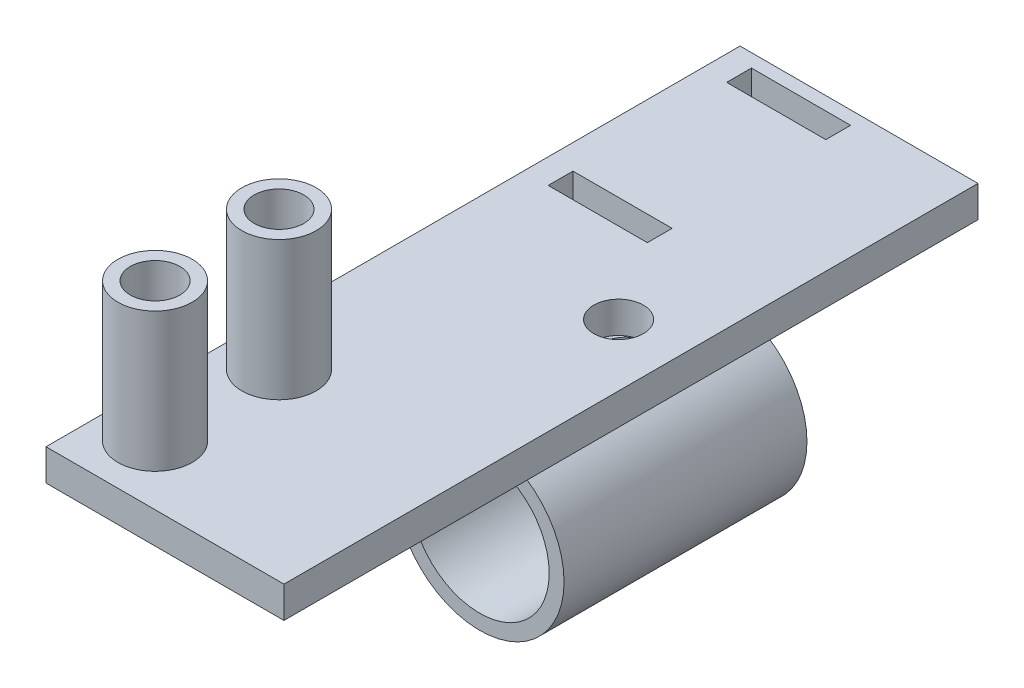
SolidWorks part; units mm, degrees
other "DetailItem2"
other "DetailItem3"
other "Weld Folder"
other "Weld Bead2"
other "Weld Bead3"
ref_plane "Front Plane" through (0, 0, 0) normal (0, 0, 1) x (1, 0, 0)
ref_plane "Top Plane" through (0, 0, 0) normal (0, 1, 0) x (1, 0, 0)
ref_plane "Right Plane" through (0, 0, 0) normal (1, 0, 0) x (0, 0, -1)
sketch "Sketch1" plane through (0, 0, 0) normal (0, 1, 0) x (1, 0, 0)
  line L0 (-59.4061, 36.8) -> (49940.5939, 36.8) construction
  line L1 (12.5, -80) -> (-35.5, -80)
  line L2 (12.5, -80) -> (12.5, 60)
  line L3 (12.5, 60) -> (-35.5, 60)
  line L4 (-35.5, -80) -> (-35.5, 60)
  line L5 (12.5, -80) -> (-35.5, 60) construction
  line L6 (12.5, 60) -> (-35.5, -80) construction
  line L7 (-30.5, 57.3) -> (-10.5, 57.3)
  line L8 (-30.5, 57.3) -> (-30.5, 52.3)
  line L9 (-30.5, 52.3) -> (-10.5, 52.3)
  line L10 (-10.5, 57.3) -> (-10.5, 52.3)
  line L11 (-30.5, 57.3) -> (-10.5, 52.3) construction
  line L12 (-30.5, 52.3) -> (-10.5, 57.3) construction
  line L13 (-10.5, 16.3) -> (-10.5, 21.3)
  line L14 (-30.5, 16.3) -> (-10.5, 16.3)
  line L15 (-30.5, 16.3) -> (-30.5, 21.3)
  line L16 (-30.5, 21.3) -> (-10.5, 21.3)
  circle A0 centre (0, 0) radius 5
  point P4 (-11.5, -10)
  point P12 (-20.5, 54.8)
  point P15 (-22.6753, 39.9204)
  point P16 (-22.8564, 42.5463)
  point P17 (-38.006, 47.3)
  point P18 (-15.3234, 47.3)
  point P19 (-10.5, 8.6186)
  dimension "D1" = 10
  dimension "D2" = 12.5
  dimension "D3" = 60
  dimension "D4" = 36.8
  dimension "D5" = 5.2
  dimension "D6" = 18
  dimension "D7" = 5
  dimension "D8" = 20
  dimension "D9" = 5
  dimension "D10" = 48
  dimension "D11" = 80
base flange "Base-Flange1" sketch "Sketch1" thickness 6.35 reverse thickness direction no parameters "D1"=10
sketch "Sketch6" plane through (0, 0, 0) normal (0, 1, 0) x (1, 0, 0)
  line L0 (-35.5, 60) -> (-35.5, -80) construction
  line L1 (-25.5, -43) -> (-25.5, -68) construction
  circle A0 centre (-25.5, -68) radius 7.5
  circle A1 centre (-25.5, -68) radius 5
  circle A2 centre (-25.5, -43) radius 7.5
  circle A3 centre (-25.5, -43) radius 5
  dimension "D3" = 10
  dimension "D4" = 15
  dimension "D1" = 10
  dimension "D2" = 68
  dimension "D5" = 25
extrude "Boss-Extrude1" add sketch "Sketch6" along normal blind 28
sketch "Sketch7" plane through (0, 0, 0) normal (0, 0, 1) x (1, 0, 0)
  line L0 (-5, -6.35) -> (5, -6.35) construction
  line L1 (-5, -6.35) -> (5, -6.35) construction
  line L2 (0, -6.35) -> (0, -23.35) construction
  circle A0 centre (0, -23.35) radius 17
  circle A1 centre (0, -23.35) radius 14
  point P8 (0, 0)
  point P9 (0, -17.8189)
  dimension "D1" = 34
  dimension "D2" = 28
extrude "Boss-Extrude2" add sketch "Sketch7" along normal blind 28 and the other way blind 21 separate body
sketch "Sketch8" plane through (0, 0, 0) normal (0, 1, 0) x (1, 0, 0)
  circle A0 centre (0, 0) radius 5 construction
  circle A1 centre (0, 0) radius 5
extrude "Cut-Extrude1" cut sketch "Sketch8" against normal through all
sketch "Bend-Lines1" [suppressed] plane through (0, 0, 0) normal (0, 1, 0) x (1, 0, 0)
sketch "Bounding-Box1" [suppressed] plane through (0, 0, 0) normal (0, 1, 0) x (1, 0, 0)
sheet metal parameters "Sheet-Metal1" thickness 6.35 parameters "D1"=10
flat pattern "Flat-Pattern1" [suppressed]
sketch "Bend-Lines2" plane through (0, 0, 0) normal (0, 1, 0) x (1, 0, 0)
sketch3d "Bounding-Box2" [suppressed]
  line L0 (-35.5, 50, 0) -> (-35.5, -80, 0) construction
  line L1 (12.5, 50, 0) -> (12.5, -80, 0) construction
  line L2 (-35.5, 50, 0) -> (12.5, 50, 0) construction
  line L3 (-35.5, -80, 0) -> (12.5, -80, 0) construction
sheet metal parameters "Sheet-Metal2" thickness 6.35 parameters "D1"=10
flat pattern "Flat-Pattern1"
sketch "Bend-Lines2" plane through (0, 0, 0) normal (0, 1, 0) x (1, 0, 0)
sketch3d "Bounding-Box2" [suppressed]
  line L0 (-35.5, 60, 0) -> (-35.5, -80, 0) construction
  line L1 (12.5, 60, 0) -> (12.5, -80, 0) construction
  line L2 (-35.5, 60, 0) -> (12.5, 60, 0) construction
  line L3 (-35.5, -80, 0) -> (12.5, -80, 0) construction
